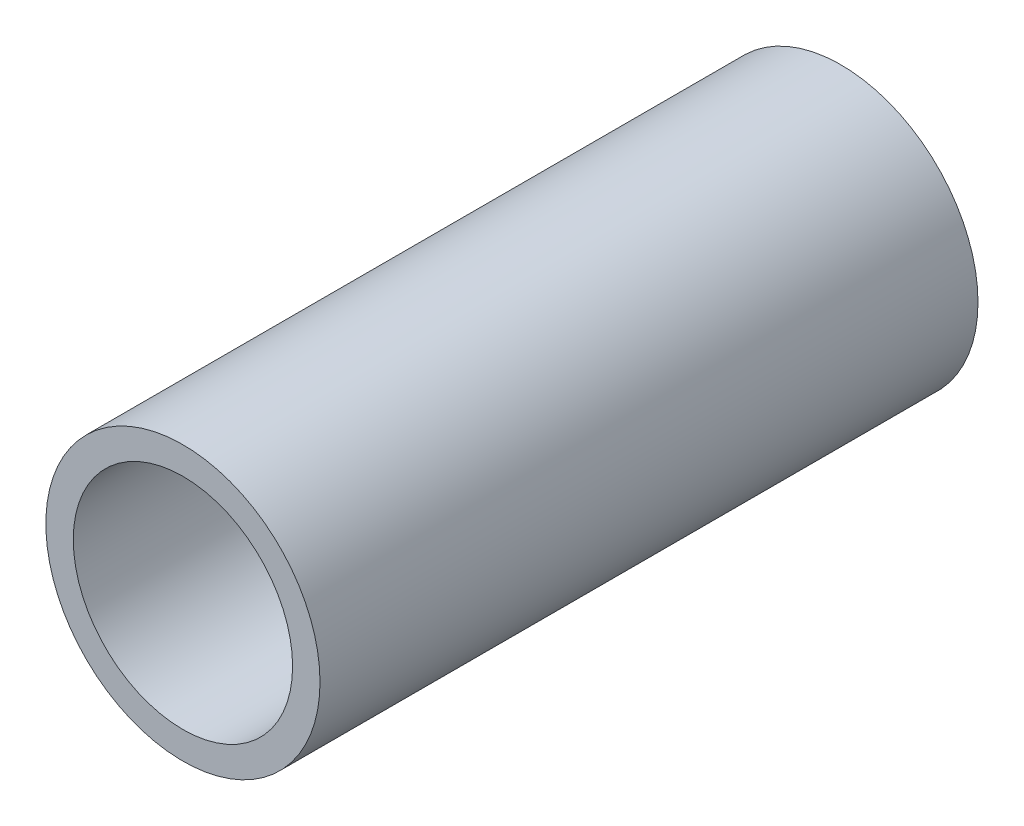
SolidWorks part; units mm, degrees
material "Nylon 101"
ref_plane "Front Plane" through (0, 0, 0) normal (0, 0, 1) x (1, 0, 0)
ref_plane "Top Plane" through (0, 0, 0) normal (0, 1, 0) x (1, 0, 0)
ref_plane "Right Plane" through (0, 0, 0) normal (1, 0, 0) x (0, 0, -1)
sketch "Sketch1" plane through (0, 0, 0) normal (0, 0, 1) x (1, 0, 0)
  circle A0 centre (0, 0) radius 6.35
  circle A1 centre (0, 0) radius 7.9375
  dimension "D1" = 12.7
  dimension "D2" = 15.875
extrude "Boss-Extrude1" add sketch "Sketch1" along normal mid plane 38.1
